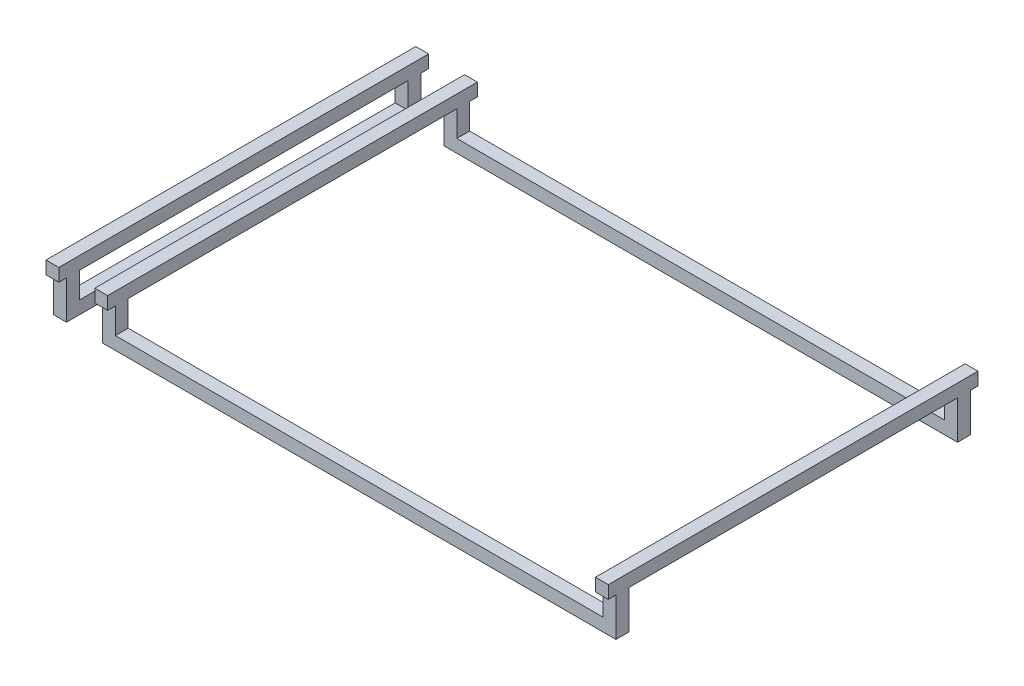
SolidWorks part; units mm, degrees
ref_plane "Plan de face" through (0, 0, 0) normal (0, 0, 1) x (1, 0, 0)
ref_plane "Plan de dessus" through (0, 0, 0) normal (0, 1, 0) x (1, 0, 0)
ref_plane "Plan de droite" through (0, 0, 0) normal (1, 0, 0) x (0, 0, -1)
sketch "Esquisse1" plane through (0, 0, 0) normal (0, 1, 0) x (1, 0, 0)
  line L0 (-204.0391, 511.3012) -> (795.9609, 511.3012)
  line L1 (-204.0391, 536.3012) -> (795.9609, 536.3012)
  line L2 (-204.0391, 536.3012) -> (-204.0391, -153.6988)
  line L3 (-204.0391, -153.6988) -> (795.9609, -153.6988)
  line L4 (795.9609, 536.3012) -> (795.9609, -153.6988)
  line L5 (-204.0391, -128.6988) -> (795.9609, -128.6988)
  line L6 (-204.0391, -153.6988) -> (-229.0391, -153.6988)
  line L7 (-229.0391, -153.6988) -> (-229.0391, 536.3012)
  line L8 (-229.0391, 536.3012) -> (-204.0391, 536.3012)
  line L9 (795.9609, 536.3012) -> (820.9609, 536.3012)
  line L10 (820.9609, 536.3012) -> (820.9609, -153.6988)
  line L11 (820.9609, -153.6988) -> (795.9609, -153.6988)
  dimension "D1" = 25
  dimension "D2" = 25
  dimension "D3" = 690
  dimension "D4" = 1000
  dimension "D5" = 25
  dimension "D6" = 25
extrude "Boss.-Extru.1" add sketch "Esquisse1" along normal blind 25 contours L5 L2 L3 L4 | L4 L1 L2 L0 | L8 L7 L6 L2 | L11 L10 L9 L4 region at (295.9609, 0, -523.8012) region at (-216.5391, 0, -191.3012) region at (808.4609, 0, -191.3012) region at (295.9609, 0, 141.1988)
sketch "Esquisse2" plane through (0, 25, 0) normal (0, 1, 0) x (1, 0, 0)
  line L1 (795.9609, -128.6988) -> (795.9609, 511.3012) construction
  line L2 (795.9609, -128.6988) -> (795.9609, 511.3012) construction
  line L3 (-204.0391, -128.6988) -> (-204.0391, 511.3012) construction
  line L4 (-204.0391, -128.6988) -> (-204.0391, 511.3012) construction
  line L5 (-229.0391, 536.3012) -> (820.9609, 536.3012) construction
  line L6 (-204.0391, -128.6988) -> (795.9609, -128.6988) construction
  circle A0 centre (-184.0391, -141.1988) radius 2.75
  circle A1 centre (775.9609, -141.1988) radius 2.75
  circle A2 centre (775.9609, 523.8012) radius 2.75
  circle A3 centre (-184.0391, 523.8012) radius 2.75
  dimension "D1" = 5.5
  dimension "D2" = 5.5
  dimension "D3" = 5.5
  dimension "D4" = 5.5
  dimension "D5" = 20
  dimension "D6" = 20
  dimension "D7" = 20
  dimension "D8" = 20
  dimension "D9" = 12.5
  dimension "D10" = 12.5
  dimension "D11" = 12.5
  dimension "D12" = 12.5
extrude "Enlèv. mat.-Extru.1" cut sketch "Esquisse2" against normal blind 2
sketch "Esquisse4" plane through (0, 0, 0) normal (0, -1, 0) x (1, 0, 0)
  line L1 (820.9609, 153.6988) -> (795.9609, 153.6988)
  line L2 (820.9609, 153.6988) -> (820.9609, 128.6988)
  line L3 (820.9609, 128.6988) -> (795.9609, 128.6988)
  line L4 (795.9609, 153.6988) -> (795.9609, 128.6988)
  line L5 (-229.0391, 153.6988) -> (-204.0391, 153.6988)
  line L6 (-229.0391, 153.6988) -> (-229.0391, 128.6988)
  line L7 (-229.0391, 128.6988) -> (-204.0391, 128.6988)
  line L8 (-204.0391, 153.6988) -> (-204.0391, 128.6988)
  line L9 (-229.0391, -536.3012) -> (-204.0391, -536.3012)
  line L10 (-229.0391, -536.3012) -> (-229.0391, -511.3012)
  line L11 (-229.0391, -511.3012) -> (-204.0391, -511.3012)
  line L12 (-204.0391, -536.3012) -> (-204.0391, -511.3012)
  line L13 (795.9609, -511.3012) -> (820.9609, -511.3012)
  line L14 (795.9609, -511.3012) -> (795.9609, -536.3012)
  line L15 (795.9609, -536.3012) -> (820.9609, -536.3012)
  line L16 (820.9609, -511.3012) -> (820.9609, -536.3012)
extrude "Boss.-Extru.3" add sketch "Esquisse4" against normal blind 75
sketch "Esquisse5" plane through (0, 75, 0) normal (0, 1, 0) x (1, 0, 0)
  line L0 (-204.0391, -153.6988) -> (795.9609, -153.6988) construction
  line L1 (795.9609, -153.6988) -> (820.9609, -153.6988)
  line L2 (795.9609, -153.6988) -> (795.9609, 536.3012)
  line L3 (795.9609, 536.3012) -> (820.9609, 536.3012)
  line L4 (820.9609, -153.6988) -> (820.9609, 536.3012)
  line L5 (-229.0391, -153.6988) -> (-204.0391, -153.6988)
  line L6 (-229.0391, -153.6988) -> (-229.0391, 536.3012)
  line L7 (-229.0391, 536.3012) -> (-204.0391, 536.3012)
  line L8 (-204.0391, -153.6988) -> (-204.0391, 536.3012)
  line L9 (-229.0391, 536.3012) -> (-204.0391, 536.3012)
  line L10 (-229.0391, 536.3012) -> (-229.0391, 556.3012)
  line L11 (-229.0391, 556.3012) -> (-204.0391, 556.3012)
  line L12 (-204.0391, 536.3012) -> (-204.0391, 556.3012)
  line L13 (-229.0391, -153.6988) -> (-204.0391, -153.6988)
  line L14 (-229.0391, -153.6988) -> (-229.0391, -173.6988)
  line L15 (-229.0391, -173.6988) -> (-204.0391, -173.6988)
  line L16 (-204.0391, -153.6988) -> (-204.0391, -173.6988)
  line L17 (795.9609, -153.6988) -> (820.9609, -153.6988)
  line L18 (795.9609, -153.6988) -> (795.9609, -173.6988)
  line L19 (795.9609, -173.6988) -> (820.9609, -173.6988)
  line L20 (820.9609, -153.6988) -> (820.9609, -173.6988)
  line L21 (795.9609, 536.3012) -> (820.9609, 536.3012)
  line L22 (795.9609, 536.3012) -> (795.9609, 556.3012)
  line L23 (795.9609, 556.3012) -> (820.9609, 556.3012)
  line L24 (820.9609, 536.3012) -> (820.9609, 556.3012)
  line L25 (-204.0391, 536.3012) -> (795.9609, 536.3012) construction
  point P20 (-216.5391, -173.6988)
  point P21 (-216.5391, 556.3012)
  point P26 (-216.5391, -153.6988)
  point P27 (808.4609, -153.6988)
  line M4 (820.9609, -153.6988) -> (820.9609, -128.6988)
  line M5 (820.9609, -128.6988) -> (795.9609, -128.6988)
  line M6 (795.9609, -128.6988) -> (795.9609, -153.6988)
  line M7 (795.9609, -153.6988) -> (820.9609, -153.6988)
  dimension "D1" = 730
  dimension "D2" = 730
  dimension "D3" = 690
  dimension "D4" = 20
  dimension "D5" = 20
extrude "Boss.-Extru.4" add sketch "Esquisse5" along normal blind 25 contours L20 L18 L19 M7 | L4 L3 L2 M5 | M7 M4 M5 M6 | L3 L24 L23 L22 | L5 L8 L7 L6 | L16 L5 L14 L15 | L7 L12 L11 L10 region at (808.4609, 75, 141.1988) region at (808.4609, 75, 163.6988) region at (808.4609, 75, -203.8012) region at (808.4609, 75, -546.3012) region at (-216.5391, 75, -191.3012) region at (-216.5391, 75, 163.6988) region at (-216.5391, 75, -546.3012)
sketch "Esquisse7" plane through (-229.0391, 0, 0) normal (-1, 0, 0) x (0, 0, 1)
  line L0 (153.6988, 0) -> (-536.3012, 0) construction
  line L1 (-511.3012, 25) -> (128.6988, 25)
  line L2 (-511.3012, 25) -> (-511.3012, 0)
  line L3 (-511.3012, 0) -> (128.6988, 0)
  line L4 (128.6988, 25) -> (128.6988, 0)
extrude "Enlèv. mat.-Extru.2" cut sketch "Esquisse7" against normal blind 1188
sketch "Esquisse8" plane through (0, 25, 0) normal (0, 1, 0) x (1, 0, 0)
  line L0 (-204.0391, 511.3012) -> (795.9609, 511.3012) construction
  line L1 (795.9609, 536.3012) -> (770.9609, 536.3012)
  line L2 (795.9609, 536.3012) -> (795.9609, 511.3012)
  line L3 (795.9609, 511.3012) -> (770.9609, 511.3012)
  line L4 (770.9609, 536.3012) -> (770.9609, 511.3012)
  line L5 (-204.0391, -128.6988) -> (795.9609, -128.6988) construction
  line L6 (795.9609, -153.6988) -> (770.9609, -153.6988)
  line L7 (795.9609, -153.6988) -> (795.9609, -128.6988)
  line L8 (795.9609, -128.6988) -> (770.9609, -128.6988)
  line L9 (770.9609, -153.6988) -> (770.9609, -128.6988)
  line L10 (-204.0391, 511.3012) -> (-204.0391, 536.3012) construction
  line L11 (-204.0391, -153.6988) -> (-179.0391, -153.6988)
  line L12 (-204.0391, -153.6988) -> (-204.0391, -128.6988)
  line L13 (-204.0391, -128.6988) -> (-179.0391, -128.6988)
  line L14 (-179.0391, -153.6988) -> (-179.0391, -128.6988)
  line L15 (-204.0391, 511.3012) -> (-179.0391, 511.3012)
  line L16 (-204.0391, 511.3012) -> (-204.0391, 536.3012)
  line L17 (-204.0391, 536.3012) -> (-179.0391, 536.3012)
  line L18 (-179.0391, 511.3012) -> (-179.0391, 536.3012)
  line L19 (-204.0391, 536.3012) -> (795.9609, 536.3012) construction
  dimension "D1" = 25
  dimension "D2" = 25
  dimension "D3" = 25
  dimension "D4" = 25
extrude "Boss.-Extru.7" add sketch "Esquisse8" along normal blind 50
sketch "Esquisse9" plane through (0, 0, -536.3012) normal (0, 0, -1) x (-1, 0, 0)
  line L1 (-820.9609, 0) -> (-795.9609, 0)
  line L2 (-820.9609, 0) -> (-820.9609, 110.2006)
  line L3 (-820.9609, 110.2006) -> (-795.9609, 110.2006)
  line L4 (-795.9609, 0) -> (-795.9609, 110.2006)
  line L5 (229.0391, 0) -> (204.0391, 0)
  line L6 (229.0391, 0) -> (229.0391, 152.2376)
  line L7 (229.0391, 152.2376) -> (204.0391, 152.2376)
  line L8 (204.0391, 0) -> (204.0391, 152.2376)
  dimension "D1" = 25
  dimension "D2" = 25
extrude "Enlèv. mat.-Extru.3" cut sketch "Esquisse9" against normal blind 926 and the other way blind 216
sketch "Esquisse10" plane through (0, 75, 0) normal (0, 1, 0) x (1, 0, 0)
  line L1 (795.9609, -153.6988) -> (770.9609, -153.6988)
  line L2 (795.9609, -153.6988) -> (795.9609, 536.3012)
  line L3 (795.9609, 536.3012) -> (770.9609, 536.3012)
  line L4 (770.9609, -153.6988) -> (770.9609, 536.3012)
  line L5 (795.9609, 536.3012) -> (770.9609, 536.3012)
  line L6 (795.9609, 536.3012) -> (795.9609, 551.3012)
  line L7 (795.9609, 551.3012) -> (770.9609, 551.3012)
  line L8 (770.9609, 536.3012) -> (770.9609, 551.3012)
  line L9 (795.9609, -153.6988) -> (770.9609, -153.6988)
  line L10 (795.9609, -153.6988) -> (795.9609, -168.6988)
  line L11 (795.9609, -168.6988) -> (770.9609, -168.6988)
  line L12 (770.9609, -153.6988) -> (770.9609, -168.6988)
  line L13 (-179.0391, -153.6988) -> (-204.0391, -153.6988)
  line L14 (-179.0391, -153.6988) -> (-179.0391, 536.3012)
  line L15 (-179.0391, 536.3012) -> (-204.0391, 536.3012)
  line L16 (-204.0391, -153.6988) -> (-204.0391, 536.3012)
  line L17 (-204.0391, 536.3012) -> (-179.0391, 536.3012)
  line L18 (-204.0391, 536.3012) -> (-204.0391, 551.3012)
  line L19 (-204.0391, 551.3012) -> (-179.0391, 551.3012)
  line L20 (-179.0391, 536.3012) -> (-179.0391, 551.3012)
  line L21 (-179.0391, -153.6988) -> (-204.0391, -153.6988)
  line L22 (-179.0391, -153.6988) -> (-179.0391, -168.6988)
  line L23 (-179.0391, -168.6988) -> (-204.0391, -168.6988)
  line L24 (-204.0391, -153.6988) -> (-204.0391, -168.6988)
  line M5 (795.9609, -153.6988) -> (795.9609, -128.6988)
  line M6 (795.9609, -128.6988) -> (770.9609, -128.6988)
  line M7 (770.9609, -128.6988) -> (770.9609, -153.6988)
  line M8 (770.9609, -153.6988) -> (795.9609, -153.6988)
  dimension "D1" = 15
  dimension "D2" = 15
  dimension "D3" = 15
  dimension "D4" = 15
extrude "Boss.-Extru.8" add sketch "Esquisse10" along normal blind 25 contours L4 L2 L3 M6 | M8 M5 M6 M7 | L12 L11 L10 M8 | L8 L3 L6 L7 | L13 L24 L23 L22 | L16 L13 L14 L15 | L15 L20 L19 L18 region at (783.4609, 75, 161.1988) region at (783.4609, 75, 141.1988) region at (783.4609, 75, -203.8012) region at (783.4609, 75, -543.8012) region at (-191.5391, 75, 161.1988) region at (-191.5391, 75, -191.3012) region at (-191.5391, 75, -543.8012)
sketch "Esquisse12" plane through (0, 100, 0) normal (0, 1, 0) x (1, 0, 0)
  line L0 (-179.0391, -168.6988) -> (-204.0391, -168.6988) construction
  line L1 (-179.0391, 551.3012) -> (-299.0391, 551.3012)
  line L2 (-179.0391, 551.3012) -> (-179.0391, -168.6988)
  line L3 (-179.0391, -168.6988) -> (-299.0391, -168.6988)
  line L4 (-299.0391, 551.3012) -> (-299.0391, -168.6988)
  line L6 (-274.0391, -168.6988) -> (-274.0391, 551.3012)
  dimension "D1" = 120
  dimension "D2" = 25
extrude "Boss.-Extru.10" add sketch "Esquisse12" against normal blind 25 separate body contours L3 L6 L1 L4 region at (-286.5391, 100, -191.3012)
sketch "Esquisse13" plane through (0, 75, 0) normal (0, -1, 0) x (-1, 0, 0)
  line L0 (274.0391, -168.6988) -> (274.0391, 551.3012) construction
  line L1 (274.0391, 536.3012) -> (299.0391, 536.3012)
  line L2 (274.0391, 536.3012) -> (274.0391, 511.3012)
  line L3 (274.0391, 511.3012) -> (299.0391, 511.3012)
  line L4 (299.0391, 536.3012) -> (299.0391, 511.3012)
  line L5 (299.0391, 551.3012) -> (299.0391, -168.6988) construction
  line L6 (274.0391, 551.3012) -> (299.0391, 551.3012) construction
  line L7 (299.0391, -153.6988) -> (274.0391, -153.6988)
  line L8 (299.0391, -153.6988) -> (299.0391, -128.6988)
  line L9 (299.0391, -128.6988) -> (274.0391, -128.6988)
  line L10 (274.0391, -153.6988) -> (274.0391, -128.6988)
  line L11 (179.0391, 536.3012) -> (204.0391, 536.3012) construction
  line L12 (204.0391, 551.3012) -> (179.0391, 551.3012) construction
  line L13 (274.0391, -168.6988) -> (299.0391, -168.6988) construction
  dimension "D1" = 25
  dimension "D2" = 25
  dimension "D3" = 15
  dimension "D4" = 15
  dimension "D5" = 15
extrude "Boss.-Extru.11" add sketch "Esquisse13" along normal up to vertex (50 mm away) up to point (-179.0391, 25, 128.6988)
sketch "Esquisse14" plane through (0, 25, 0) normal (0, -1, 0) x (-1, 0, 0)
  line L1 (274.0391, -153.6988) -> (299.0391, -153.6988)
  line L2 (274.0391, -153.6988) -> (274.0391, 536.3012)
  line L3 (274.0391, 536.3012) -> (299.0391, 536.3012)
  line L4 (299.0391, -153.6988) -> (299.0391, 536.3012)
extrude "Boss.-Extru.12" add sketch "Esquisse14" along normal blind 25
